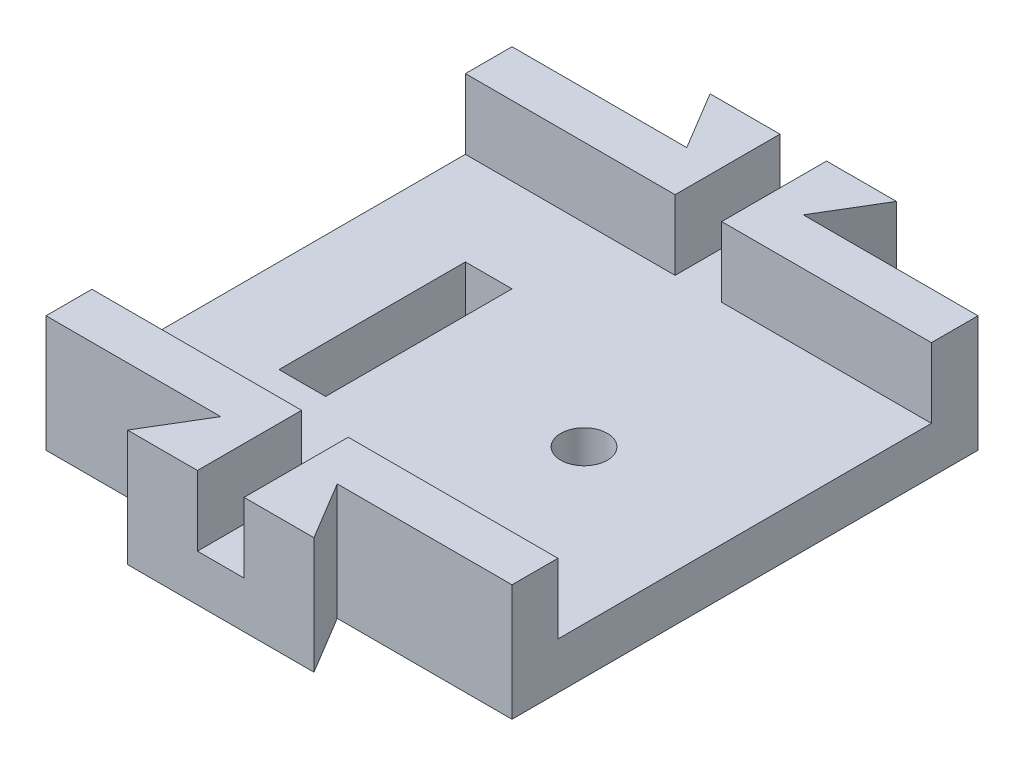
SolidWorks part; units mm, degrees
ref_plane "Front Plane" through (0, 0, 0) normal (0, 0, 1) x (1, 0, 0)
ref_plane "Top Plane" through (0, 0, 0) normal (0, 1, 0) x (1, 0, 0)
ref_plane "Right Plane" through (0, 0, 0) normal (1, 0, 0) x (0, 0, -1)
sketch "Sketch1" plane through (0, 0, 0) normal (0, 1, 0) x (1, 0, 0)
  line L1 (-59.3211, 174.9321) -> (140.6789, 174.9321)
  line L2 (-59.3211, 174.9321) -> (-59.3211, -25.0679)
  line L3 (-59.3211, -25.0679) -> (140.6789, -25.0679)
  line L4 (140.6789, 174.9321) -> (140.6789, -25.0679)
  line L5 (-19.3211, 34.9321) -> (0.6789, 34.9321)
  line L6 (-19.3211, 34.9321) -> (-19.3211, 114.9321)
  line L7 (-19.3211, 114.9321) -> (0.6789, 114.9321)
  line L8 (0.6789, 34.9321) -> (0.6789, 114.9321)
  dimension "D1" = 60
  dimension "D2" = 60
  dimension "D3" = 40
extrude "Boss-Extrude1" add sketch "Sketch1" along normal blind 50
shell "Shell1" thickness 20 removed face at (40.6789, 50, -74.9321)
sketch "Sketch3" plane through (0, 0, 0) normal (0, -1, 0) x (-1, 0, 0)
sketch "Sketch4" plane through (0, 50, 0) normal (0, 1, 0) x (1, 0, 0)
  line L0 (-39.3211, 14.9321) -> (-39.3211, 134.9321)
  line L1 (-39.3211, 134.9321) -> (20.6789, 134.9321)
  line L2 (20.6789, 134.9321) -> (20.6789, 14.9321)
  line L3 (20.6789, 14.9321) -> (-39.3211, 14.9321)
extrude "Cut-Extrude1" cut sketch "Sketch4" against normal blind 30
sketch "Sketch5" plane through (0, 0, 0) normal (0, -1, 0) x (1, 0, 0)
  line L0 (40.6789, 25.0679) -> (15.6789, 25.0679)
  line L1 (-59.3211, 25.0679) -> (140.6789, 25.0679) construction
  line L2 (15.6789, 25.0679) -> (0.6789, 50.0679)
  line L3 (0.6789, 50.0679) -> (80.6789, 50.0679)
  line L4 (80.6789, 50.0679) -> (65.6789, 25.0679)
  line L5 (65.6789, 25.0679) -> (40.6789, 25.0679)
  line L7 (19.067, 29.7324) -> (61.7771, 29.7324)
  line L8 (61.7771, 29.7324) -> (73.0332, 45.955)
  line L9 (73.0332, 45.955) -> (10.5603, 45.955)
  line L10 (10.5603, 45.955) -> (19.067, 29.7324)
  dimension "D1" = 25
  dimension "D2" = 25
  dimension "D3" = 25
  dimension "D4" = 25
  dimension "D5" = 60
  dimension "D6" = 60
extrude "Boss-Extrude2" add sketch "Sketch5" against normal blind 50 contours L3 L4 L5 L0 L2
sketch "Sketch6" plane through (0, 50, 0) normal (0, 1, 0) x (1, 0, 0)
  line L0 (30.6789, -50.0679) -> (30.6789, -5.0679)
  line L1 (0.6789, -50.0679) -> (80.6789, -50.0679) construction
  line L2 (-39.3211, -5.0679) -> (120.6789, -5.0679) construction
  line L3 (30.6789, -5.0679) -> (50.6789, -5.0679)
  line L4 (50.6789, -5.0679) -> (50.6789, -50.0679)
  line L5 (50.6789, -50.0679) -> (30.6789, -50.0679)
  dimension "D1" = 15
  dimension "D2" = 15
extrude "Cut-Extrude2" cut sketch "Sketch6" against normal blind 30
ref_plane "Plane1" through (0, 0, -74.9321) normal (0, 0, 1) x (1, 0, 0)
mirror "Mirror1" about plane through (0, 0, -74.9321) normal (0, 0, 1) of "Cut-Extrude2", "Boss-Extrude2"
sketch "Sketch7" plane through (0, 0, 0) normal (0, -1, 0) x (-1, 0, 0)
  circle A0 centre (-74.8357, 71.6847) radius 10
extrude "Cut-Extrude3" cut sketch "Sketch7" against normal blind 28 contours A0
sketch "Sketch8" plane through (140.6789, 0, 0) normal (1, 0, 0) x (0, 0, -1)
  line L0 (154.9321, 50) -> (154.9321, 20)
  line L1 (-25.0679, 50) -> (174.9321, 50) construction
  line L2 (154.9321, 20) -> (-5.3609, 20)
  line L3 (-5.3609, 20) -> (-5.3609, 50)
  line L4 (-5.3609, 50) -> (154.9321, 50)
  point P4 (165.551, 50)
extrude "Cut-Extrude4" cut sketch "Sketch8" against normal blind 213
